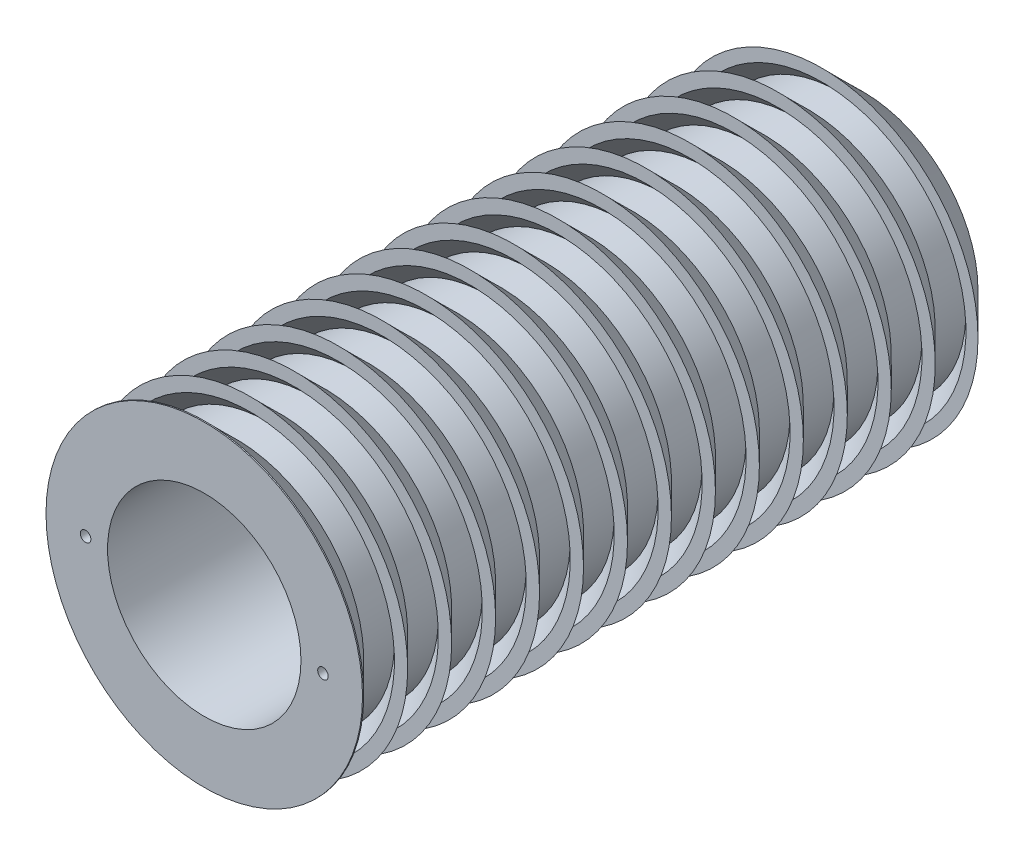
SolidWorks part; units mm, degrees
ref_plane "Plano frontal" through (0, 0, 0) normal (0, 0, 1) x (1, 0, 0)
ref_plane "Plano superior" through (0, 0, 0) normal (0, 1, 0) x (1, 0, 0)
ref_plane "Plano direito" through (0, 0, 0) normal (1, 0, 0) x (0, 0, -1)
sketch "Esboço1" plane through (0, 0, 0) normal (0, 0, 1) x (1, 0, 0)
  circle A0 centre (0, 0) radius 36
  dimension "D1" = 72
extrude "Ressalto-extrusão1" add sketch "Esboço1" along normal blind 150
sketch "Esboço2" plane through (0, 0, 0) normal (0, 1, 0) x (1, 0, 0)
  line L0 (-36, -9.4613) -> (-32.7155, -9.4613)
  line L1 (-36, 0) -> (-36, -150) construction
  line L2 (-32.7155, -9.4613) -> (-28.9655, -5.7113)
  line L3 (-28.9655, -5.7113) -> (-28.9655, -12.694)
  line L4 (-28.9655, -12.694) -> (-36, -19.7286)
  line L5 (-36, -19.7286) -> (-36, -9.4613)
  line L6 (0, 0) -> (0, -150) construction
  line L7 (-36, -150) -> (36, -150) construction
revolve "Corte-Revolução1" cut sketch "Esboço2" angle 360 about L6
sketch "Esboço3" plane through (0, 0, 0) normal (0, 1, 0) x (1, 0, 0)
  line L0 (0, 0) -> (0, -150) construction
  line L1 (-36, -150) -> (36, -150) construction
pattern_linear "Padrão linear1" count 14 spacing 10 along (0, 0, 1) of "Corte-Revolução1"
chamfer "Chanfro1" distance 10 angle 45 1 edges at (36, 0, 0)
sketch "Esboço4" plane through (0, 0, 150) normal (0, 0, 1) x (1, 0, 0)
  circle A0 centre (0, 0) radius 22
  dimension "D1" = 44
extrude "Corte-extrusão1" cut sketch "Esboço4" against normal blind 134
sketch "Esboço5" plane through (0, 0, 150) normal (0, 0, 1) x (1, 0, 0)
  circle A0 centre (-27, 0) radius 1.2
  circle A1 centre (27, 0) radius 1.2
  dimension "D1" = 2.4
  dimension "D2" = 2.4
  dimension "D3" = 54
  dimension "D4" = 27
extrude "Corte-extrusão2" cut sketch "Esboço5" against normal blind 134
